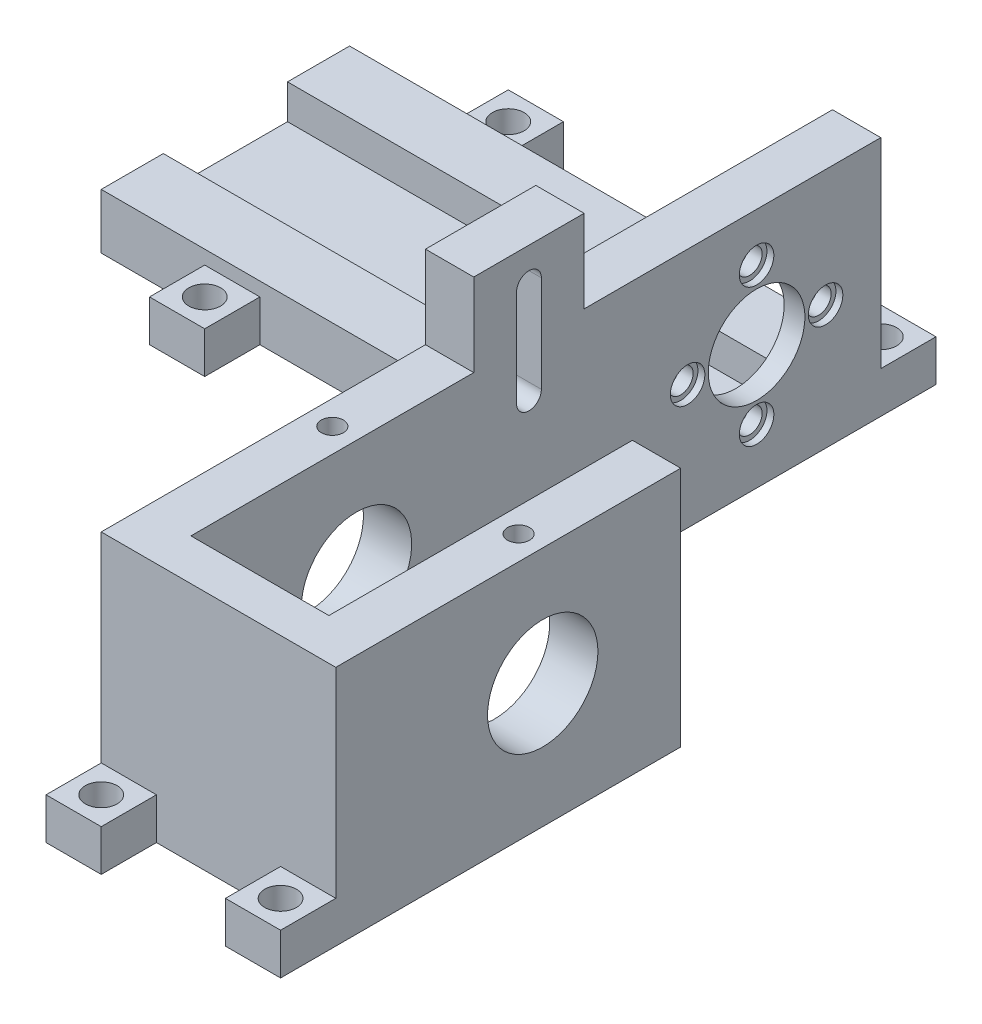
SolidWorks part; units mm, degrees
ref_plane "Plan de face" through (0, 0, 0) normal (0, 0, 1) x (1, 0, 0)
ref_plane "Plan de dessus" through (0, 0, 0) normal (0, 1, 0) x (1, 0, 0)
ref_plane "Plan de droite" through (0, 0, 0) normal (1, 0, 0) x (0, 0, -1)
sketch "Esquisse1" plane through (0, 0, 0) normal (0, 1, 0) x (1, 0, 0)
  line L0 (0, 0) -> (17, 0)
  line L1 (0, 0) -> (-17, 0)
  line L2 (17, 0) -> (17, 50)
  line L3 (17, 50) -> (10, 50)
  line L4 (10, 50) -> (10, 6)
  line L5 (10, 6) -> (-10, 6)
  line L6 (-17, 0) -> (-17, 106)
  line L7 (-10, 6) -> (-10, 106)
  line L8 (-10, 106) -> (-17, 106)
  line L9 (-10, 106) -> (-70, 106)
  line L10 (-70, 106) -> (-70, 76)
  line L11 (-70, 76) -> (-10, 76)
extrude "Boss.-Extru.1" add sketch "Esquisse1" along normal blind 35 contours L6 L11 L7 L8 | L11 L6 L1 L0 L2 L3 L4 L5 L7 region at (-8.5, 0, -0.8326) region at (-13.5, 0, -91)
sketch "Esquisse2" plane through (17, 0, 0) normal (1, 0, 0) x (0, 0, -1)
  line L0 (30, 18) -> (30, 0) construction
  line L2 (0, 0) -> (50, 0) construction
  line L3 (30, 0) -> (0, 0) construction
  circle A0 centre (30, 18) radius 8
extrude "Enlèv. mat.-Extru.1" cut sketch "Esquisse2" against normal blind 28 contours A0 region at (17, 18, -30)
sketch "Esquisse4" plane through (-17, 0, 0) normal (-1, 0, 0) x (0, 0, 1)
  line L0 (-30, 18) -> (-88, 18) construction
  line L1 (-88, 18) -> (-98, 18) construction
  line L2 (-88, 18) -> (-88, 8) construction
  line L4 (-88, 8) -> (-88, 0) construction
  line L5 (-98, 18) -> (-88, 18) construction
  line L6 (-88, 18) -> (-88, 28) construction
  line L7 (-88, 28) -> (-88, 18) construction
  line L8 (-88, 18) -> (-78, 18) construction
  line L9 (-78, 18) -> (-88, 18) construction
  line L10 (0, 0) -> (-106, 0) construction
  line L11 (-88, 0) -> (-70, 0) construction
  line L12 (-70, 0) -> (-79, 0) construction
  line L15 (-70, 8) -> (-70, 0)
  line L16 (-70, 0) -> (-88, 0) construction
  line L17 (-88, 0) -> (-106, 0) construction
  line L18 (-106, 0) -> (-97, 0) construction
  line L21 (-106, 35) -> (-106, 0) construction
  line L22 (-106, 8) -> (-106, 0)
  line L23 (-106, 0) -> (-97, 0)
  line L24 (-79, 0) -> (-70, 0)
  line L26 (-97, 0) -> (-97, 8)
  line L27 (-97, 8) -> (-106, 8)
  line L28 (-70, 8) -> (-79, 8)
  line L29 (-79, 8) -> (-79, 0)
  line L30 (-97, 0) -> (-97, 3)
  line L31 (-97, 3) -> (-79, 3)
  line L32 (-79, 3) -> (-79, 0)
  circle A0 centre (-88, 18) radius 13.4
  circle A1 centre (-88, 18) radius 7
  circle A2 centre (-88, 8) radius 1.8
  circle A3 centre (-78, 18) radius 1.8
  circle A4 centre (-88, 28) radius 1.8
  circle A5 centre (-98, 18) radius 1.8
  line M3 (-106, 0) -> (0, 0)
  line M6 (-106, 35) -> (-106, 0)
extrude "Enlèv. mat.-Extru.2" cut sketch "Esquisse4" against normal blind 10 contours A5 | A4 | A2 | A3 region at (-17, 8, -88) region at (-17, 18, -78) region at (-17, 28, -88) region at (-17, 18, -98)
extrude "Enlèv. mat.-Extru.3" cut sketch "Esquisse4<3>" against normal blind 4 contours A0 A5 A4 A3 A2 A1 region at (-17, 18, -101.021)
sketch "Esquisse4<3>" plane through (-17, 0, 0) normal (-1, 0, 0) x (0, 0, 1) same geometry as "Esquisse4"
extrude "Enlèv. mat.-Extru.4" cut sketch "Esquisse4<4>" against normal blind 10 contours A1 region at (-17, 18, -88)
sketch "Esquisse4<4>" plane through (-17, 0, 0) normal (-1, 0, 0) x (0, 0, 1) same geometry as "Esquisse4"
extrude "Boss.-Extru.2" add sketch "Esquisse4<11>" along normal blind 55 contours L26 L27 M6 M3 | L28 L29 L15 M3 | L31 L26 L29 M3 region at (-17, 4, -74.5) region at (-17, 1.5, -88) region at (-17, 4, -101.5)
sketch "Esquisse4<11>" plane through (-17, 0, 0) normal (-1, 0, 0) x (0, 0, 1) same geometry as "Esquisse4"
sketch "Esquisse8" plane through (0, 0, 0) normal (0, -1, 0) x (1, 0, 0)
  line L0 (17, 0) -> (17, 8)
  line L1 (17, 8) -> (9, 8)
  line L2 (9, 8) -> (9, 0)
  line L3 (17, 0) -> (-17, 0) construction
  line L4 (9, 0) -> (17, 0)
  line L5 (-17, 0) -> (-17, 8)
  line L6 (-17, 8) -> (-9, 8)
  line L7 (-9, 8) -> (-9, 0)
  line L8 (-9, 0) -> (-17, 0)
  line L9 (-72, -106) -> (-72, -114)
  line L10 (-72, -114) -> (-64, -114)
  line L11 (-64, -114) -> (-64, -106)
  line L12 (-64, -106) -> (-72, -106)
  line L13 (-72, -70) -> (-72, -62)
  line L14 (-72, -62) -> (-64, -62)
  line L15 (-64, -62) -> (-64, -70)
  line L16 (-72, -70) -> (-17, -70) construction
  line L17 (-64, -70) -> (-72, -70)
  line L18 (9, 8) -> (17, 0) construction
  line L19 (17, 8) -> (9, 0) construction
  line L20 (-9, 0) -> (-17, 8) construction
  line L21 (-17, 0) -> (-9, 8) construction
  line L22 (-72, -62) -> (-64, -70) construction
  line L23 (-64, -62) -> (-72, -70) construction
  line L24 (-64, -114) -> (-72, -106) construction
  line L25 (-72, -114) -> (-64, -106) construction
  line L26 (-10, -106) -> (-10, -114)
  line L27 (-10, -114) -> (-18, -114)
  line L28 (-18, -114) -> (-18, -106)
  line L29 (-10, -106) -> (-72, -106) construction
  line L30 (-18, -106) -> (-10, -106)
  line L31 (-18, -106) -> (-10, -114) construction
  line L32 (-10, -106) -> (-18, -114) construction
  circle A0 centre (-68, -66) radius 2.3
  circle A1 centre (-68, -110) radius 2.3
  circle A2 centre (13, 4) radius 2.3
  circle A3 centre (-13, 4) radius 2.3
  circle A4 centre (-14, -110) radius 2.3
extrude "Boss.-Extru.3" add sketch "Esquisse8" against normal blind 6
sketch "Esquisse10" plane through (-17, 0, 0) normal (-1, 0, 0) x (0, 0, 1)
  line L0 (-55, 47) -> (-55, 35) construction
  line L1 (-47, 35) -> (-47, 47)
  line L2 (-47, 47) -> (-63, 47)
  line L7 (0, 35) -> (-106, 35) construction
  line L12 (-55, 35) -> (-47, 35) construction
  line L13 (-63, 47) -> (-63, 35)
  line L14 (-63, 35) -> (-47, 35)
extrude "Boss.-Extru.4" add sketch "Esquisse10" against normal blind 7
sketch "Esquisse9" plane through (-17, 0, 0) normal (-1, 0, 0) x (0, 0, 1)
  line L0 (-55, 18) -> (0, 18) construction
  line L1 (-55, 18) -> (-55, 28) construction
  line L2 (-53.2, 28) -> (-53.2, 42)
  line L3 (-55, 18) -> (-55, 43) construction
  line L4 (-56.8, 42) -> (-56.8, 28)
  line L5 (0, 35) -> (0, 6) construction
  circle A7 centre (-55, 28) radius 1.8
  circle A8 centre (-55, 42) radius 1.8
extrude "Enlèv. mat.-Extru.5" cut sketch "Esquisse9" against normal blind 10 contours A7 | A8 L4 A7 L2 | A8 region at (-17, 35, -55) region at (-17, 28, -55) region at (-17, 42, -55)
sketch "Esquisse11" plane through (0, 35, 0) normal (0, 1, 0) x (1, 0, 0)
  line L0 (17, 0) -> (17, 30) construction
  line L1 (17, 0) -> (17, 50) construction
  line L2 (17, 30) -> (10, 30) construction
  line L3 (10, 50) -> (10, 6) construction
  line L4 (-17, 0) -> (-17, 30) construction
  line L5 (-17, 0) -> (-17, 47) construction
  line L6 (-17, 30) -> (-10, 30) construction
  line L7 (-10, 6) -> (-10, 47) construction
  circle A0 centre (-13.5, 30) radius 1.6
  circle A1 centre (13.5, 30) radius 1.6
extrude "Enlèv. mat.-Extru.6" cut sketch "Esquisse11" against normal blind 10 contours A0 | A1
sketch "Esquisse12" plane through (-10, 0, 0) normal (1, 0, 0) x (0, 0, -1)
  circle A0 centre (88, 28) radius 2.5
  circle A1 centre (98, 18) radius 2.5
  circle A2 centre (88, 8) radius 2.5
  circle A3 centre (78, 18) radius 2.5
extrude "Enlèv. mat.-Extru.7" cut sketch "Esquisse12" against normal blind 1
sketch "Esquisse15" plane through (-11, 0, 0) normal (1, 0, 0) x (0, 0, -1)
  circle A0 centre (30, 18) radius 8
extrude "Enlèv. mat.-Extru.8" cut sketch "Esquisse15" against normal blind 10
sketch "Esquisse16" plane through (-72, 0, 0) normal (-1, 0, 0) x (0, 0, 1)
  line L0 (-106, 8) -> (-106, 0)
  line L1 (-114, 0) -> (-62, 0) construction
  line L2 (-106, 0) -> (-70, 0)
  line L3 (-70, 0) -> (-70, 8)
  line L4 (-70, 8) -> (-79, 8)
  line L5 (-79, 8) -> (-79, 3)
  line L6 (-79, 3) -> (-97, 3)
  line L7 (-97, 3) -> (-97, 8)
  line L8 (-97, 8) -> (-106, 8)
extrude "Boss.-Extru.5" add sketch "Esquisse16" along normal blind 15
